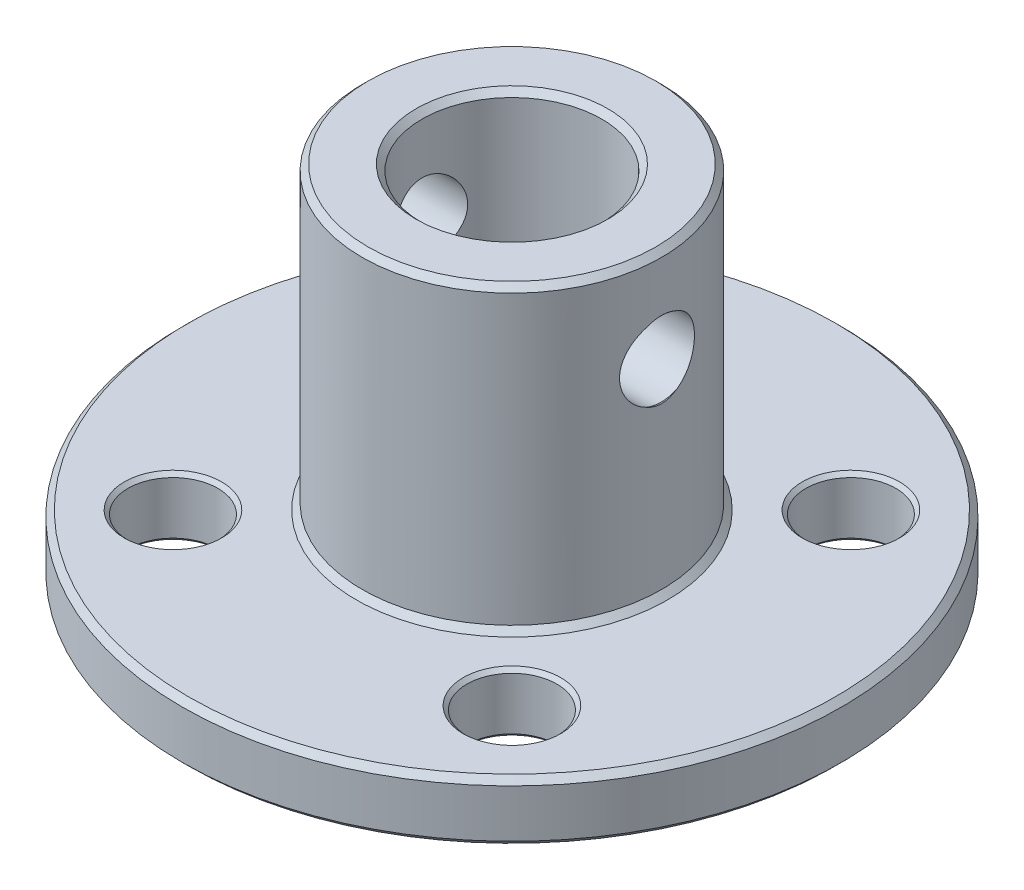
SolidWorks part; units mm, degrees
ref_plane "Front Plane" through (0, 0, 0) normal (0, 0, 1) x (1, 0, 0)
ref_plane "Top Plane" through (0, 0, 0) normal (0, 1, 0) x (1, 0, 0)
ref_plane "Right Plane" through (0, 0, 0) normal (1, 0, 0) x (0, 0, -1)
sketch "Sketch1" plane through (0, 0, 0) normal (0, 1, 0) x (1, 0, 0)
  circle A0 centre (0, 0) radius 11
  dimension "D1" = 22
extrude "Flange" add sketch "Sketch1" along normal blind 2
sketch "Sketch2" plane through (0, 2, 0) normal (0, 1, 0) x (1, 0, 0)
  circle A0 centre (0, 0) radius 5
  dimension "D1" = 10
extrude "Collar" add sketch "Sketch2" along normal blind 10
sketch "Sketch3" plane through (0, 12, 0) normal (0, 1, 0) x (1, 0, 0)
  circle A0 centre (0, 0) radius 3
  dimension "D1" = 6
extrude "Cut-Extrude1" cut sketch "Sketch3" against normal through all
sketch "Sketch4" plane through (0, 0, 0) normal (0, 0, 1) x (1, 0, 0)
  line L0 (5, 12) -> (-5, 12) construction
  line L1 (5, 2) -> (5, 12) construction
  line L2 (-5, 12) -> (-5, 2) construction
  point P0 (5, 8.85)
  point P1 (-5, 8.85)
  dimension "D1" = 3.15
hole_wizard "Set Screw Tap 1" positions "3DSketch1" profile "Sketch7" hole size "M3x0.5" standard "ANSI Metric" end condition up to next
sketch3d "3DSketch1"
  point P0 (5, 8.85, 0)
  point P3 (5, 8.85, 0)
  point P6 (5, 8.85, 0)
  point P8 (5, 8.85, 0)
  point P10 (5, 8.85, 0)
  point P11 (4.7841, 8.7941, -1.4533)
sketch "Sketch7" plane through (5, 8.85, 0) normal (0, 1, 0) x (0, 0, -1)
  line L0 (0, 0) -> (0, 5)
  line L1 (0, 5) -> (1.25, 5)
  line L2 (1.25, 5) -> (1.25, 0.025)
  line L3 (1.25, 0.025) -> (1.275, 0)
  line L5 (1.275, 0) -> (0, 0)
  line L6 (-1.25, 0.025) -> (-1.275, 0) construction
  line L11 (0, -6.35) -> (0, 107.95) construction
  dimension "Thru Hole Dia." = 2.5
  dimension "Thru Hole Depth" = 5
  dimension "Near C'Sink Dia." = 2.55
  dimension "Near C'Sink Angle" = 90
hole_wizard "Set Screw Tap 2" positions "3DSketch3" profile "Sketch9" hole size "M3x0.5" standard "ANSI Metric" end condition up to next
sketch3d "3DSketch3"
  point P0 (-5, 8.85, 0)
  point P4 (-5, 8.85, 0)
  point P7 (-5, 8.85, 0)
  point P11 (-5, 8.85, 0)
sketch "Sketch9" plane through (-5, 8.85, 0) normal (0, 1, 0) x (0, 0, 1)
  line L0 (0, 0) -> (0, 8.001)
  line L1 (0, 8.001) -> (1.25, 8.001)
  line L2 (1.25, 8.001) -> (1.25, 0.025)
  line L3 (1.25, 0.025) -> (1.275, 0)
  line L5 (1.275, 0) -> (0, 0)
  line L6 (-1.25, 0.025) -> (-1.275, 0) construction
  line L11 (0, -6.35) -> (0, 107.95) construction
  dimension "Thru Hole Dia." = 2.5
  dimension "Thru Hole Depth" = 8.001
  dimension "Near C'Sink Dia." = 2.55
  dimension "Near C'Sink Angle" = 90
sketch "Sketch10" plane through (0, 2, 0) normal (0, 1, 0) x (1, 0, 0)
  line L1 (-5.6569, -5.6569) -> (5.6569, -5.6569) construction
  line L2 (-5.6569, -5.6569) -> (-5.6569, 5.6569) construction
  line L3 (-5.6569, 5.6569) -> (5.6569, 5.6569) construction
  line L4 (5.6569, -5.6569) -> (5.6569, 5.6569) construction
  line L5 (-5.6569, -5.6569) -> (5.6569, 5.6569) construction
  line L6 (-5.6569, 5.6569) -> (5.6569, -5.6569) construction
  point P0 (0, 0)
  point P7 (-5.6569, 5.6569)
  point P8 (-5.6569, -5.6569)
  point P9 (5.6569, -5.6569)
  point P10 (5.6569, 5.6569)
  dimension "D1" = 16
hole_wizard "Flange Holes" positions "Sketch10" profile "Sketch11" hole size "M3" standard "ANSI Metric" end condition up to next
sketch "Sketch11" plane through (0, 2, 0) normal (1, 0, 0) x (0, 0, 1)
  line L0 (0, 0) -> (0, 2)
  line L1 (0, 2) -> (1.625, 2)
  line L2 (1.5, 1.875) -> (1.5, 0.125)
  line L3 (1.5, 0.125) -> (1.625, 0)
  line L5 (1.625, 0) -> (0, 0)
  line L6 (-1.5, 0.125) -> (-1.625, 0) construction
  line L7 (1.625, 2) -> (1.5, 1.875)
  line L8 (-1.625, 2) -> (-1.5, 1.875) construction
  line L11 (0, -6.35) -> (0, 107.95) construction
  dimension "Thru Hole Dia." = 3
  dimension "Thru Hole Depth" = 2
  dimension "Near C'Sink Dia." = 3.25
  dimension "Near C'Sink Angle" = 90
  dimension "Far C'Sink Dia." = 3.25
  dimension "Far C'Sink Angle" = 90
chamfer "Body Chamfers" distance 0.2 6 edges at (0, 2, 5) (0, 0, 3) (0, 12, 3) (0, 12, 5) (0, 0, 11) (0, 2, 11)
